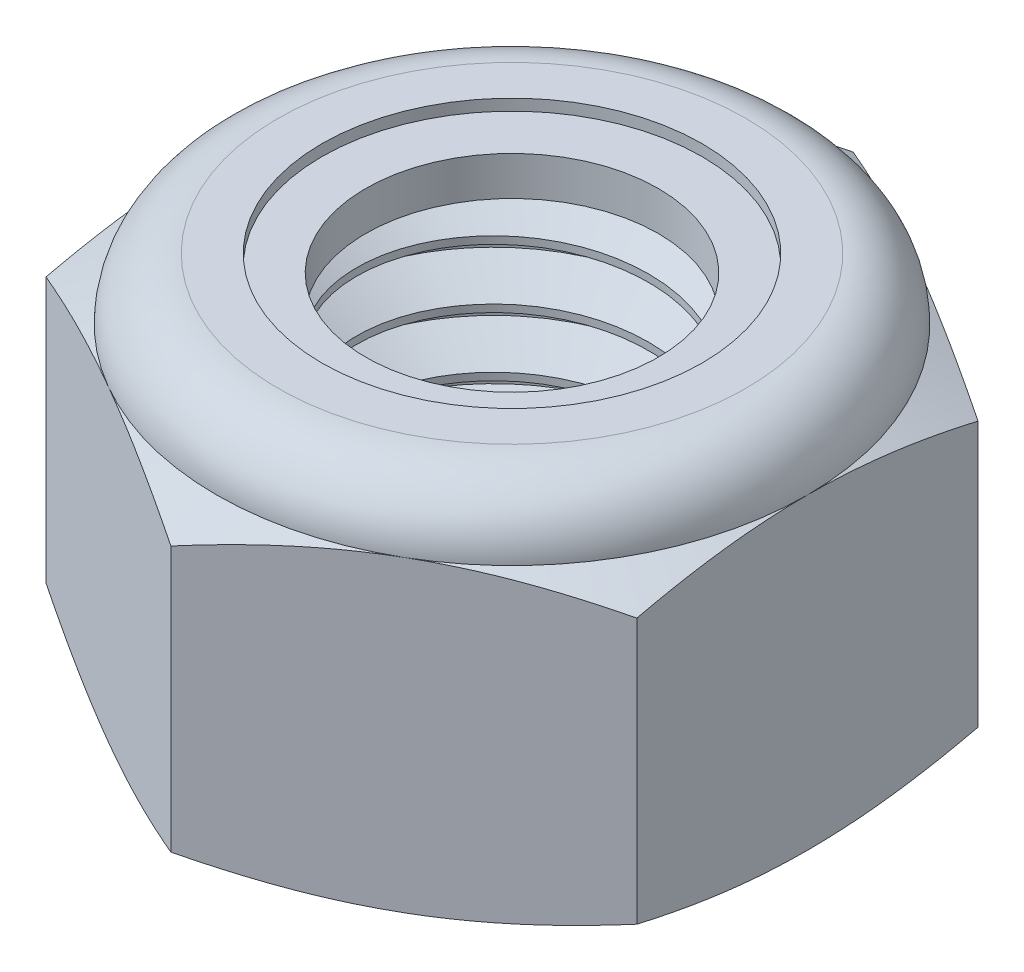
SolidWorks part; units mm, degrees
material "Plain Carbon Steel"
ref_plane "Front" through (0, 0, 0) normal (0, 0, 1) x (1, 0, 0)
ref_plane "Top" through (0, 0, 0) normal (0, 1, 0) x (1, 0, 0)
ref_plane "Right" through (0, 0, 0) normal (1, 0, 0) x (0, 0, -1)
sketch "Sketch1" plane through (0, 0, 0) normal (0, 1, 0) x (1, 0, 0)
  line L1 (0, 4.6188) -> (-4, 2.3094)
  line L2 (-4, 2.3094) -> (-4, -2.3094)
  line L3 (-4, -2.3094) -> (0, -4.6188)
  line L4 (0, -4.6188) -> (4, -2.3094)
  line L5 (4, -2.3094) -> (4, 2.3094)
  line L6 (4, 2.3094) -> (0, 4.6188)
  circle A0 centre (0, 0) radius 4 construction
  dimension "Hex Flats" = 8
extrude "Extrude1" add sketch "Sketch1" along normal blind 5
sketch "Sketch2" plane through (0, 0, 0) normal (1, 0, 0) x (0, 0, -1)
  line L0 (-2.5, 0) -> (-2.5, 5) construction
  line L1 (0, 0) -> (2.5, 0)
  line L2 (0, 0) -> (0, 5)
  line L3 (0, 5) -> (2.5, 5)
  line L4 (2.5, 0) -> (2.5, 5)
  line L5 (-2.3094, 5) -> (2.3094, 5) construction
  line L7 (0, -2.5) -> (0, 0) construction
  dimension "Thread Dia" = 5
revolve "Revolve1" add sketch "Sketch2" angle 360 about L7
sketch "Sketch8" plane through (0, 0, 0) normal (0, -1, 0) x (1, 0, 0)
  circle A1 centre (0, 0) radius 2.5
  circle A2 centre (0, 0) radius 2.5
  dimension "D1" = 0
curve "Helix/Spiral1" pitch 0.8 height 5.8 turns 7.25 parameters "Pitch"=0.8
sketch "Sketch9" plane through (0, 0, 0) normal (1, 0, 0) x (0, 0, -1)
  line L0 (2.5, -0.7) -> (2.5, 0)
  line L1 (2.5, -0.7) -> (1.9804, -0.4)
  line L2 (1.9804, -0.4) -> (1.9804, -0.3)
  line L3 (1.9804, -0.3) -> (2.5, 0)
  line L4 (-2.5, 0) -> (2.5, 0) construction
  line L5 (2.5, -0.35) -> (1.9804, -0.35) construction
  line L6 (2.2402, -0.55) -> (2.2402, -0.15) construction
  dimension "D1" = 0.1
  dimension "D2" = 0.4
  dimension "D3" = 60
sweep "Cut-Sweep1" cut profiles "Sketch9" path "Helix/Spiral1" align with end faces yes
sketch "Sketch10" plane through (0, 0, 0) normal (0, -1, 0) x (1, 0, 0)
  circle A1 centre (0, 0) radius 2.5
  circle A2 centre (0, 0) radius 2.5
  dimension "D1" = 0
extrude "Boss-Extrude1" add sketch "Sketch10" against normal through all draft 45
sketch "Sketch11" plane through (0, 5, 0) normal (0, 1, 0) x (1, 0, 0)
  circle A1 centre (0, 0) radius 2.5
  circle A2 centre (0, 0) radius 2.5
  dimension "D1" = 0
extrude "Boss-Extrude2" add sketch "Sketch11" against normal through all draft 45
combine bodies "Combine1" operation type subtract main body 108 bodies to subtract 134
sketch "Sketch5" plane through (0, 0, 0) normal (1, 0, 0) x (0, 0, -1)
  line L0 (0, 0) -> (4, 0)
  line L1 (4, 0) -> (4.6188, 0.2886)
  line L2 (4.6188, 0.2886) -> (4.6188, 3.8781)
  line L3 (4.6188, 3.8781) -> (4, 4.1667)
  line L4 (3.1667, 5) -> (3.1667, 6.27)
  line L5 (3.1667, 6.27) -> (5.8888, 6.27)
  line L6 (5.8888, 6.27) -> (5.8888, -1.27)
  line L7 (5.8888, -1.27) -> (0, -1.27)
  line L8 (0, -1.27) -> (0, 0)
  line L9 (4, 4.1667) -> (4, 0) construction
  line L10 (0, 0) -> (2.5, 0) construction
  line L13 (4.6188, 2.0833) -> (5.8888, 2.0833) construction
  line L14 (4.6188, 5) -> (4.6188, 0) construction
  line L15 (0, 0) -> (0, 6.27) construction
  line L20 (0, 6.27) -> (3.1667, 6.27) construction
  line L22 (0, 5) -> (2.5, 5) construction
  arc A0 (4, 4.1667) -> (3.1667, 5) centre (3.1667, 4.1667) ccw
  dimension "D1" = 25
  dimension "D2" = 1.27
  dimension "D3" = 5
  dimension "D4" = 0.8333
revolve "Cut-Revolve3" cut sketch "Sketch5" angle 360 about L15
sketch "Sketch6" plane through (0, 0, 0) normal (1, 0, 0) x (0, 0, -1)
  line L0 (0, 4.1667) -> (3.8476, 4.1667)
  line L1 (3.1667, 4.8476) -> (2.5735, 4.8476)
  line L2 (0, 6.27) -> (0, 4.1667)
  line L3 (2.5735, 6.27) -> (0, 6.27)
  line L4 (0, 6.27) -> (3.1667, 6.27) construction
  line L5 (0, 0) -> (0, 6.27) construction
  line L6 (0, 6.27) -> (0, 0) construction
  line L7 (2.5735, 4.8476) -> (2.5735, 6.27)
  line L8 (3.1667, 5) -> (3.1667, 4.8476) construction
  line L9 (2.5735, 4.8476) -> (1.9804, 4.8476) construction
  line L10 (1.9804, 4.8476) -> (1.9804, 9.6243) construction
  line L11 (-2.5, 0) -> (2.5, 0) construction
  arc A0 (3.8476, 4.1667) -> (3.1667, 4.8476) centre (3.1667, 4.1667) ccw
  arc A1 (4, 4.1667) -> (3.1667, 5) centre (3.1667, 4.1667) ccw construction
  dimension "D1" = 0.1524
revolve "Cut-Revolve4" cut sketch "Sketch6" angle 360 about L6
sketch "Sketch7" plane through (0, 0, 0) normal (1, 0, 0) x (0, 0, -1)
  line L0 (1.9804, 4.2429) -> (3.7666, 4.2429)
  line L1 (3.1667, 4.7714) -> (1.9804, 4.7714)
  line L2 (1.9804, 4.7714) -> (1.9804, 4.2429)
  line L3 (1.9804, 4.2429) -> (0, 4.2429) construction
  line L4 (0, 4.2429) -> (0, 4.7714) construction
  line L5 (0, 4.7714) -> (1.9804, 4.7714) construction
  line L6 (1.9804, 4.2429) -> (1.9804, 4.1667) construction
  line L7 (0, 4.1667) -> (3.8476, 4.1667) construction
  line L8 (3.1667, 4.7714) -> (3.1667, 4.8476) construction
  arc A0 (3.7666, 4.2429) -> (3.1667, 4.7714) centre (3.1667, 4.1667) ccw
  arc A2 (3.8476, 4.1667) -> (3.1667, 4.8476) centre (3.1667, 4.1667) ccw construction
  dimension "D1" = 0.0762
revolve "Revolve2" add sketch "Sketch7" angle 360 about L4
equation "\"D4@Sketch5\"=\"Height@Extrude1\"/6"
equation "\"D3@Helix/Spiral1\"=\"Pitch@Helix/Spiral1\"+\"Height@Extrude1\""
equation "\"D1@Sketch9\"=\"Pitch@Helix/Spiral1\"*.125"
equation "\"D2@Sketch9\"=\"Pitch@Helix/Spiral1\"*.50"
